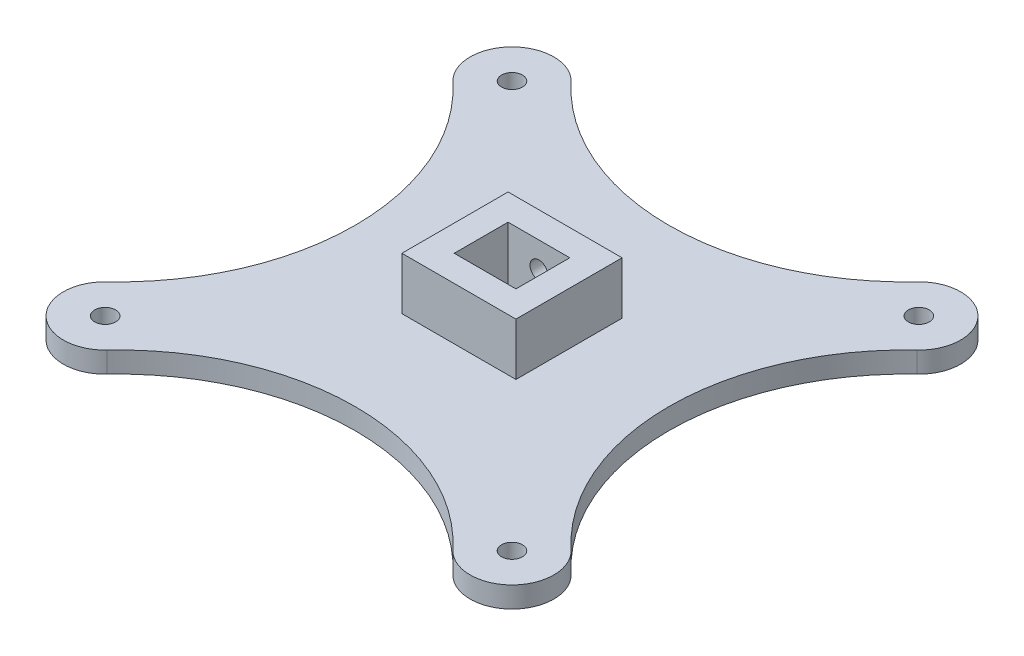
SolidWorks part; units mm, degrees
material "PET"
ref_plane "Front Plane" through (0, 0, 0) normal (0, 0, 1) x (1, 0, 0)
ref_plane "Top Plane" through (0, 0, 0) normal (0, 1, 0) x (1, 0, 0)
ref_plane "Right Plane" through (0, 0, 0) normal (1, 0, 0) x (0, 0, -1)
sketch "Sketch1" plane through (0, 0, 0) normal (0, 1, 0) x (1, 0, 0)
  line L22 (0, -55) -> (0, 55) construction
  line L23 (-38.8909, 38.8909) -> (38.8909, -38.8909) construction
  line L24 (38.8909, 38.8909) -> (-38.8909, -38.8909) construction
  line L29 (0, 30) -> (0, -30) construction
  line L31 (-30, 0) -> (30, 0) construction
  circle A8 centre (0, 0) radius 55 construction
  circle A9 centre (-38.8909, 38.8909) radius 2
  circle A10 centre (38.8909, 38.8909) radius 2
  circle A11 centre (38.8909, -38.8909) radius 2
  circle A12 centre (-38.8909, -38.8909) radius 2
  arc A13 (-33.0446, 44.3518) -> (-44.3518, 33.0446) centre (-38.8909, 38.8909) ccw
  arc A14 (44.3518, 33.0446) -> (33.0446, 44.3518) centre (38.8909, 38.8909) ccw
  arc A15 (33.0446, -44.3518) -> (44.3518, -33.0446) centre (38.8909, -38.8909) ccw
  arc A16 (-44.3518, -33.0446) -> (-33.0446, -44.3518) centre (-38.8909, -38.8909) ccw
  arc A17 (-44.3518, 33.0446) -> (-44.3518, -33.0446) centre (-75.2181, 0) cw
  arc A18 (44.3518, 33.0446) -> (44.3518, -33.0446) centre (75.2181, 0) ccw
  arc A19 (-33.0446, 44.3518) -> (33.0446, 44.3518) centre (0, 75.2181) ccw
  arc A20 (-33.0446, -44.3518) -> (33.0446, -44.3518) centre (0, -75.2181) cw
  point P14 (0, 0)
  point P34 (0, 0)
  dimension "D1" = 60
  dimension "D6" = 4
  dimension "D7" = 110
  dimension "D8" = 8
extrude "Boss-Extrude1" add sketch "Sketch1" along normal blind 4
sketch "Sketch7" plane through (0, 4, 0) normal (0, -1, 0) x (1, 0, 0)
  line L0 (-10.9, 10.15) -> (10.9, 10.15)
  line L1 (-5.9, -5.15) -> (5.9, -5.15)
  line L2 (-5.9, -5.15) -> (-5.9, 5.15)
  line L3 (-5.9, 5.15) -> (5.9, 5.15)
  line L4 (5.9, -5.15) -> (5.9, 5.15)
  line L5 (-5.9, -5.15) -> (5.9, 5.15) construction
  line L6 (-5.9, 5.15) -> (5.9, -5.15) construction
  line L7 (10.9, -10.15) -> (10.9, 10.15)
  line L8 (-10.9, -10.15) -> (10.9, -10.15)
  line L9 (-10.9, -10.15) -> (-10.9, 10.15)
  point P0 (0, 0)
  dimension "D1" = 11.8
  dimension "D2" = 10.3
  dimension "D3" = 5
extrude "Boss-Extrude2" add sketch "Sketch7" against normal blind 10
hole_wizard "M3 Clearance Hole1" positions "3DSketch1" profile "Sketch8" hole size "M3" standard "ISO" end condition up to next
sketch3d "3DSketch1"
  line L0 (10.9, 14, -10.15) -> (10.9, 4, -10.15) construction
  line L2 (-10.9, 14, -10.15) -> (10.9, 14, -10.15) construction
  point P0 (0, 9, -10.15)
  point P8 (0, 9.0774, -10.15)
  dimension "D1" = 10.9
  dimension "D2" = 5
sketch "Sketch8" plane through (0, 9, -10.15) normal (1, 0, 0) x (0, 1, 0)
  line L0 (0, 0) -> (0, 5)
  line L1 (0, 5) -> (1.7, 5)
  line L2 (1.7, 5) -> (1.7, 0)
  line L5 (1.7, 0) -> (0, 0)
  line L11 (0, -6.35) -> (0, 107.95) construction
  dimension "Thru Hole Dia." = 3.4
  dimension "Thru Hole Depth" = 5
extrude "Cut-Extrude1" cut sketch "Sketch7<2>" along normal blind 10 contours L3 L4 L1 L2
sketch "Sketch7<2>" plane through (0, 4, 0) normal (0, -1, 0) x (1, 0, 0) same geometry as "Sketch7"
